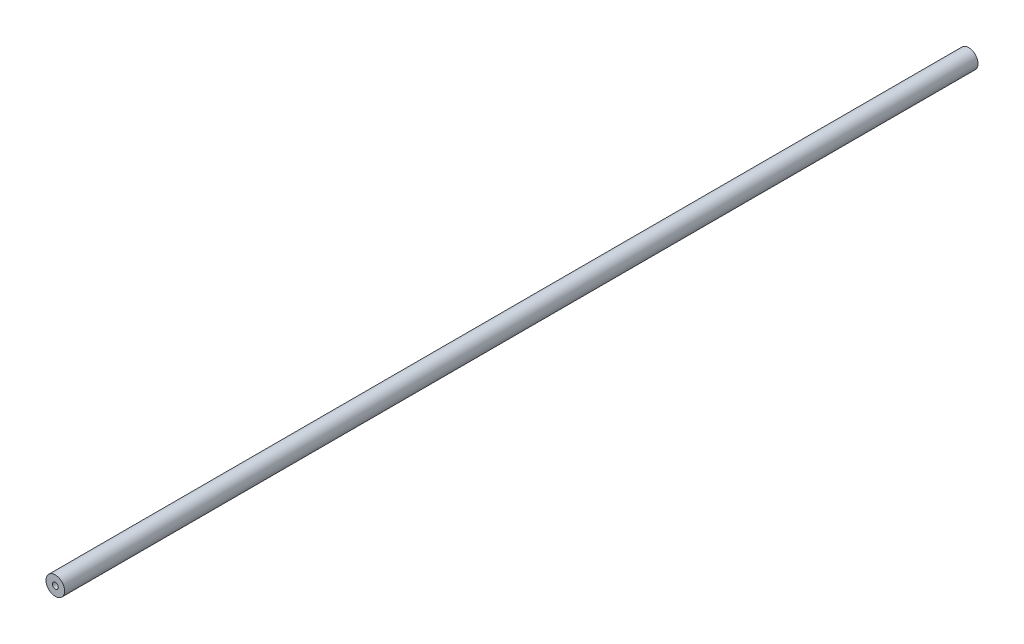
SolidWorks part; units mm, degrees
material "6061-T6 (SS)"
ref_plane "Front Plane" through (0, 0, 0) normal (0, 0, 1) x (1, 0, 0)
ref_plane "Top Plane" through (0, 0, 0) normal (0, 1, 0) x (1, 0, 0)
ref_plane "Right Plane" through (0, 0, 0) normal (1, 0, 0) x (0, 0, -1)
sketch "Sketch1" plane through (0, 0, 0) normal (0, 0, 1) x (1, 0, 0)
  circle A0 centre (0, 0) radius 6.35
  dimension "D1" = 12.7
extrude "Boss-Extrude1" add sketch "Sketch1" along normal blind 622.3
hole_wizard "#10-32 Tapped Hole1" positions "Sketch3" profile "Sketch2" tap size "#10-32" standard "ANSI Inch"
sketch "Sketch3" plane through (0, 0, 622.3) normal (0, 0, 1) x (1, 0, 0)
  point P0 (0, 0)
sketch "Sketch2" plane through (0, 0, 622.3) normal (1, 0, 0) x (0, -1, 0)
  line L0 (0, 0) -> (0, 14.9293)
  line L1 (0, 14.9293) -> (2.0193, 13.716)
  line L2 (2.0193, 13.716) -> (2.0193, 0)
  line L5 (2.0193, 0) -> (0, 0)
  line L10 (0, 14.9293) -> (-2.0193, 13.716) construction
  line L11 (0, -6.35) -> (0, 107.95) construction
  dimension "Tap Drill Dia." = 4.0386
  dimension "Tap Drill Depth" = 13.716
  dimension "Drill Angle" = 118
cosmetic thread "Hole Thread1"
hole_wizard "#10-32 Tapped Hole2" positions "Sketch5" profile "Sketch4" tap size "#10-32" standard "ANSI Inch"
sketch "Sketch5" plane through (0, 0, 0) normal (0, 0, -1) x (-1, 0, 0)
  point P0 (0, 0)
sketch "Sketch4" plane through (0, 0, 0) normal (1, 0, 0) x (0, 1, 0)
  line L0 (0, 0) -> (0, 14.9293)
  line L1 (0, 14.9293) -> (2.0193, 13.716)
  line L2 (2.0193, 13.716) -> (2.0193, 0)
  line L5 (2.0193, 0) -> (0, 0)
  line L10 (0, 14.9293) -> (-2.0193, 13.716) construction
  line L11 (0, -6.35) -> (0, 107.95) construction
  dimension "Tap Drill Dia." = 4.0386
  dimension "Tap Drill Depth" = 13.716
  dimension "Drill Angle" = 118
cosmetic thread "Hole Thread2"
